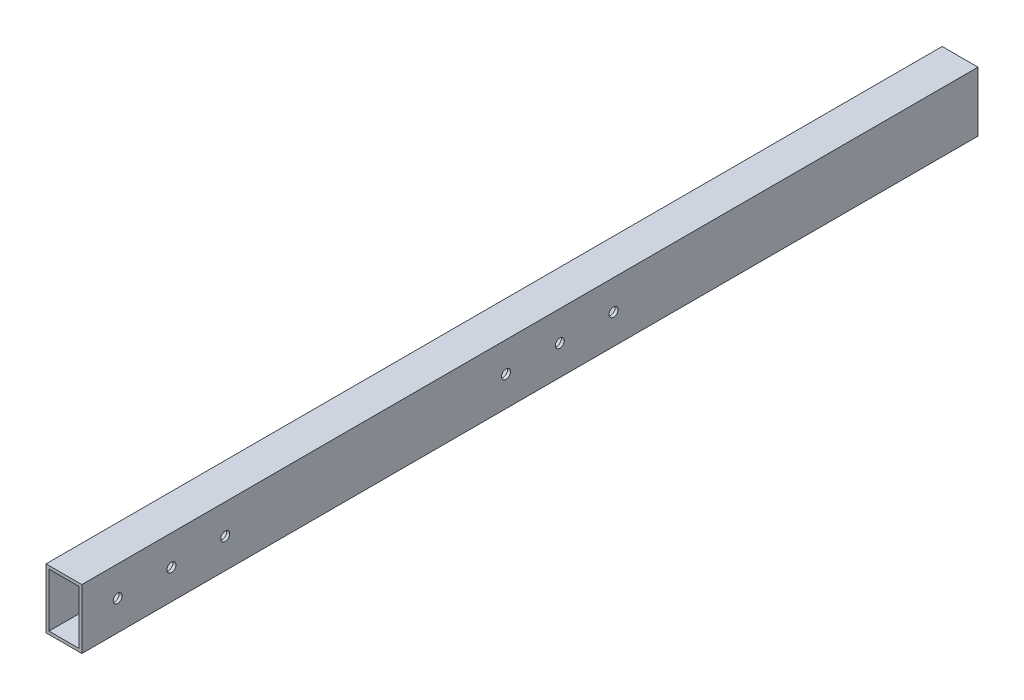
SolidWorks part; units mm, degrees
ref_plane "Front Plane" through (0, 0, 0) normal (0, 0, 1) x (1, 0, 0)
ref_plane "Top Plane" through (0, 0, 0) normal (0, 1, 0) x (1, 0, 0)
ref_plane "Right Plane" through (0, 0, 0) normal (1, 0, 0) x (0, 0, -1)
sketch "Sketch1" plane through (0, 0, 0) normal (0, 0, 1) x (1, 0, 0)
  line L1 (6, -10) -> (-6, -10)
  line L2 (6, -10) -> (6, 10)
  line L3 (6, 10) -> (-6, 10)
  line L4 (-6, -10) -> (-6, 10)
  line L5 (6, -10) -> (-6, 10) construction
  line L6 (6, 10) -> (-6, -10) construction
  line L7 (5, -9) -> (-5, -9)
  line L8 (5, -9) -> (5, 9)
  line L9 (5, 9) -> (-5, 9)
  line L10 (-5, -9) -> (-5, 9)
  line L11 (5, -9) -> (-5, 9) construction
  line L12 (5, 9) -> (-5, -9) construction
  point P0 (0, 0)
  point P6 (0, 0)
  dimension "D1" = 20
  dimension "D2" = 12
  dimension "D3" = 1
  dimension "D4" = 1
extrude "Boss-Extrude1" add sketch "Sketch1" along normal blind 300
sketch "Sketch2" plane through (6, 0, 0) normal (1, 0, 0) x (0, 0, -1)
  line L0 (-300, 0) -> (0, 0) construction
  line L1 (-300, -10) -> (-300, 10) construction
  line L2 (-300, -10) -> (0, -10) construction
  line L3 (-150, 0) -> (-150, 117.5205) construction
  line L4 (0, -10) -> (0, 10) construction
  line L5 (-300, 10) -> (-240, 10) construction
  line L6 (-300, 10) -> (-300, -10) construction
  line L7 (-300, -10) -> (-240, -10) construction
  line L8 (-240, 10) -> (-240, -10) construction
  circle A0 centre (-140, 0) radius 1.5
  circle A1 centre (-122, 0) radius 1.5
  circle A2 centre (-158, 0) radius 1.5
  circle A3 centre (-270, 0) radius 1.5
  circle A4 centre (-288, 0) radius 1.5
  circle A5 centre (-252, 0) radius 1.5
  dimension "D1" = 3
  dimension "D5" = 3
  dimension "D2" = 140
  dimension "D3" = 18
  dimension "D4" = 18
  dimension "D6" = 18
  dimension "D7" = 18
  dimension "D8" = 60
  dimension "D9" = 30
extrude "Cut-Extrude1" cut sketch "Sketch2" against normal blind 200
